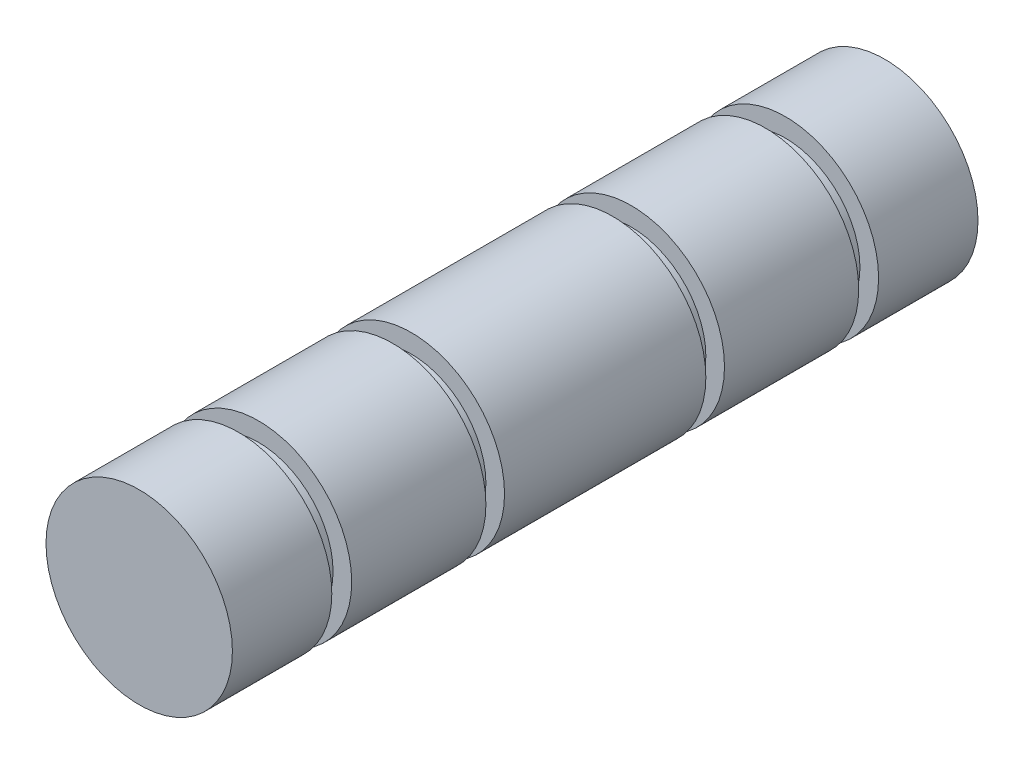
SolidWorks part; units mm, degrees
ref_plane "Front Plane" through (0, 0, 0) normal (0, 0, 1) x (1, 0, 0)
ref_plane "Top Plane" through (0, 0, 0) normal (0, 1, 0) x (1, 0, 0)
ref_plane "Right Plane" through (0, 0, 0) normal (1, 0, 0) x (0, 0, -1)
sketch "Sketch1" plane through (0, 0, 0) normal (0, 0, 1) x (1, 0, 0)
  circle A0 centre (0, 0) radius 4.7625
  dimension "D1" = 9.525
extrude "Boss-Extrude1" add sketch "Sketch1" along normal mid plane 38.1
sketch "Sketch2" plane through (0, 0, 0) normal (0, 1, 0) x (1, 0, 0)
  line L0 (4.7625, -19.05) -> (4.7625, 19.05) construction
  line L1 (4.7625, 13.97) -> (3.81, 13.97)
  line L2 (4.7625, 13.97) -> (4.7625, 12.954)
  line L3 (4.7625, 12.954) -> (3.81, 12.954)
  line L4 (3.81, 13.97) -> (3.81, 12.954)
  line L5 (4.7625, 19.05) -> (-4.7625, 19.05) construction
  line L6 (4.7625, -12.954) -> (3.81, -12.954)
  line L7 (4.7625, -12.954) -> (4.7625, -13.97)
  line L8 (4.7625, -13.97) -> (3.81, -13.97)
  line L9 (3.81, -12.954) -> (3.81, -13.97)
  line L10 (-4.7625, -19.05) -> (4.7625, -19.05) construction
  line L11 (4.7625, -19.05) -> (4.7625, 19.05) construction
  line L12 (4.7625, 6.096) -> (3.81, 6.096)
  line L13 (4.7625, 6.096) -> (4.7625, 5.1435)
  line L14 (4.7625, 5.1435) -> (3.81, 5.1435)
  line L15 (3.81, 6.096) -> (3.81, 5.1435)
  line L17 (4.7625, -5.1435) -> (3.81, -5.1435)
  line L18 (4.7625, -5.1435) -> (4.7625, -6.096)
  line L19 (4.7625, -6.096) -> (3.81, -6.096)
  line L20 (3.81, -5.1435) -> (3.81, -6.096)
  point P10 (3.81, 13.462)
  dimension "D1" = 0.9525
  dimension "D2" = 0.9525
  dimension "D3" = 1.016
  dimension "D4" = 1.016
  dimension "D5" = 5.08
  dimension "D6" = 5.08
  dimension "D7" = 0.9525
  dimension "D8" = 0.9525
  dimension "D9" = 6.858
  dimension "D10" = 0.9525
  dimension "D11" = 0.9525
  dimension "D12" = 6.858
ref_axis "Axis1" through (0, 0, 19.05) along (0, 0, -1)
revolve "Cut-Revolve1" cut sketch "Sketch2" angle 360 about axis through (0, 0, 19.05) along (0, 0, -1)
